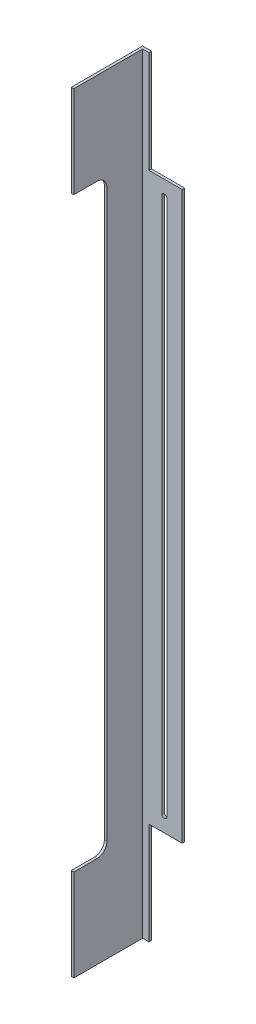
SolidWorks part; units mm, degrees
material "Простая углеродистая сталь"
ref_plane "Спереди" through (0, 0, 0) normal (0, 0, 1) x (1, 0, 0)
ref_plane "Сверху" through (0, 0, 0) normal (0, 1, 0) x (1, 0, 0)
ref_plane "Справа" through (0, 0, 0) normal (1, 0, 0) x (0, 0, -1)
sketch "Эскиз1" plane through (0, 0, 0) normal (0, 0, 1) x (1, 0, 0)
  line L0 (16.5, 111) -> (10.5, 111) construction
  line L1 (3.5, 0) -> (16.5, 0)
  line L2 (0, 0) -> (0, 222)
  line L3 (3.5, 222) -> (16.5, 222)
  line L4 (16.5, 0) -> (16.5, 222)
  line L5 (10.5, 217) -> (8.5, 217)
  line L6 (10.5, 217) -> (10.5, 5)
  line L7 (10.5, 5) -> (8.5, 5)
  line L8 (8.5, 217) -> (8.5, 5)
  line L9 (3.5, 262) -> (0, 262)
  line L10 (0, 222) -> (0, 262)
  line L11 (3.5, 0) -> (3.5, -40)
  line L12 (3.5, -40) -> (0, -40)
  line L13 (0, 0) -> (0, -40)
  line L14 (3.5, 222) -> (3.5, 262)
  dimension "D1" = 212
  dimension "D2" = 222
  dimension "D3" = 16.5
  dimension "D4" = 6
  dimension "D5" = 2
  dimension "D6" = 13
  dimension "D7" = 40
extrude "Бобышка-Вытянуть1" add sketch "Эскиз1" along normal blind 1
fillet "Скругление1" radius 1 4 edges at (8.5, 5, 0.5) (10.5, 5, 0.5) (10.5, 217, 0.5) (8.5, 217, 0.5)
sketch "Эскиз2" plane through (0, 0, 0) normal (-1, 0, 0) x (0, 0, 1)
  line L0 (1, 262) -> (1, -40) construction
  line L1 (0, -40) -> (28, -40)
  line L2 (0, -40) -> (0, 262)
  line L3 (0, 262) -> (28, 262)
  line L4 (28, -40) -> (28, -4)
  line L5 (28, 226) -> (28, 262)
  line L6 (28, 226) -> (15, 226)
  line L8 (28, -4) -> (15, -4)
  line L9 (15, 226) -> (15, -4)
  dimension "D1" = 27
  dimension "D2" = 230
  dimension "D3" = 15
extrude "Бобышка-Вытянуть2" add sketch "Эскиз2" against normal blind 1
fillet "Скругление2" radius 4 2 edges at (0.5, -4, 15) (0.5, 226, 15)
